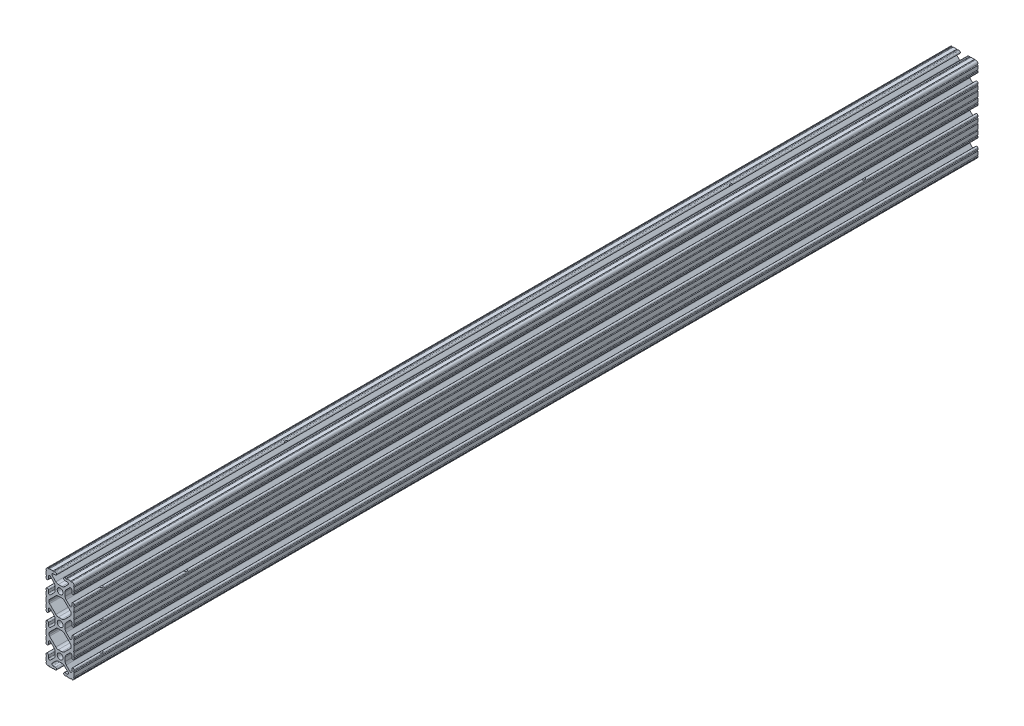
SolidWorks part; units mm, degrees
ref_plane "Front" through (0, 0, 0) normal (0, 0, 1) x (1, 0, 0)
ref_plane "Top" through (0, 0, 0) normal (0, 1, 0) x (1, 0, 0)
ref_plane "Right" through (0, 0, 0) normal (1, 0, 0) x (0, 0, -1)
sketch "Sketch1" plane through (0, 0, 0) normal (0, 0, 1) x (1, 0, 0)
  line L0 (-7.4908, -34.8742) -> (7.4908, -34.8742) construction
  line L1 (-3.1974, -36.9951) -> (3.1974, -36.9951) construction
  line L2 (-7.4908, 34.8742) -> (7.4908, 34.8742) construction
  line L3 (-3.1974, 36.9951) -> (3.1974, 36.9951) construction
  line L16 (-9.9314, -12.1463) -> (-9.9314, -13.2537)
  line L17 (-3.8759, -5.4384) -> (-9.4702, -11.0327)
  line L18 (1.6308, -4.5085) -> (-1.6308, -4.5085)
  line L19 (9.4702, -11.0327) -> (3.8759, -5.4384)
  line L20 (9.9314, -13.2537) -> (9.9314, -12.1463)
  line L21 (3.8759, -19.9616) -> (9.4702, -14.3673)
  line L22 (-1.6308, -20.8915) -> (1.6308, -20.8915)
  line L23 (-9.4702, -14.3673) -> (-3.8759, -19.9616)
  line L32 (-9.9314, 13.2537) -> (-9.9314, 12.1463)
  line L33 (-3.8759, 19.9616) -> (-9.4702, 14.3673)
  line L34 (1.6308, 20.8915) -> (-1.6308, 20.8915)
  line L35 (9.4702, 14.3673) -> (3.8759, 19.9616)
  line L36 (9.9314, 12.1463) -> (9.9314, 13.2537)
  line L37 (3.8759, 5.4384) -> (9.4702, 11.0327)
  line L38 (-1.6308, 4.5085) -> (1.6308, 4.5085)
  line L39 (-9.4702, 11.0327) -> (-3.8759, 5.4384)
  line L152 (-12.7, 34.9504) -> (-12.7, 31.7246)
  line L153 (-12.7, 30.7086) -> (-12.7, 29.7023)
  line L154 (-10.4902, 29.7023) -> (-10.4902, 31.8748)
  line L155 (-8.7558, 32.5932) -> (-5.4384, 29.2759)
  line L156 (-4.5085, 27.0308) -> (-4.5085, 23.7692)
  line L157 (-5.4384, 21.5241) -> (-8.7558, 18.2068)
  line L158 (-10.4902, 18.9252) -> (-10.4902, 21.0977)
  line L159 (-12.7, 21.0977) -> (-12.7, 20.0914)
  line L160 (-12.7, 19.0754) -> (-12.7, 15.8496)
  line L161 (-12.7, 14.8336) -> (-12.7, 10.5664)
  line L162 (-12.7, 9.5504) -> (-12.7, 6.3246)
  line L163 (-12.7, 5.3086) -> (-12.7, 4.3023)
  line L164 (-10.4902, 4.3023) -> (-10.4902, 6.4748)
  line L165 (-8.7558, 7.1932) -> (-5.4384, 3.8759)
  line L166 (-4.5085, 1.6308) -> (-4.5085, -1.6308)
  line L167 (-5.4384, -3.8759) -> (-8.7558, -7.1932)
  line L168 (-10.4902, -6.4748) -> (-10.4902, -4.3023)
  line L169 (-12.7, -4.3023) -> (-12.7, -5.3086)
  line L170 (-12.7, -6.3246) -> (-12.7, -9.5504)
  line L171 (-12.7, -10.5664) -> (-12.7, -14.8336)
  line L172 (-12.7, -15.8496) -> (-12.7, -19.0754)
  line L173 (-12.7, -20.0914) -> (-12.7, -21.0977)
  line L174 (-10.4902, -21.0977) -> (-10.4902, -18.9252)
  line L175 (-8.7558, -18.2068) -> (-5.4384, -21.5241)
  line L176 (-4.5085, -23.7692) -> (-4.5085, -27.0308)
  line L177 (-5.4384, -29.2759) -> (-8.7558, -32.5932)
  line L178 (-10.4902, -31.8748) -> (-10.4902, -29.7023)
  line L179 (-12.7, -29.7023) -> (-12.7, -30.7086)
  line L180 (-12.7, -31.7246) -> (-12.7, -34.9504)
  line L181 (-9.5504, -38.1) -> (-6.3246, -38.1)
  line L182 (-5.3086, -38.1) -> (-4.3023, -38.1)
  line L183 (-4.3023, -35.8902) -> (-6.4748, -35.8902)
  line L184 (-7.1932, -34.1558) -> (-3.8759, -30.8384)
  line L185 (-1.6308, -29.9085) -> (1.6308, -29.9085)
  line L186 (3.8759, -30.8384) -> (7.1932, -34.1558)
  line L187 (6.4748, -35.8902) -> (4.3023, -35.8902)
  line L188 (4.3023, -38.1) -> (5.3086, -38.1)
  line L189 (6.3246, -38.1) -> (9.5504, -38.1)
  line L190 (12.7, -34.9504) -> (12.7, -31.7246)
  line L191 (12.7, -30.7086) -> (12.7, -29.7023)
  line L192 (10.4902, -29.7023) -> (10.4902, -31.8748)
  line L193 (8.7558, -32.5932) -> (5.4384, -29.2759)
  line L194 (4.5085, -27.0308) -> (4.5085, -23.7692)
  line L195 (5.4384, -21.5241) -> (8.7558, -18.2068)
  line L196 (10.4902, -18.9252) -> (10.4902, -21.0977)
  line L197 (12.7, -21.0977) -> (12.7, -20.0914)
  line L198 (12.7, -19.0754) -> (12.7, -15.8496)
  line L199 (12.7, -14.8336) -> (12.7, -10.5664)
  line L200 (12.7, -9.5504) -> (12.7, -6.3246)
  line L201 (12.7, -5.3086) -> (12.7, -4.3023)
  line L202 (10.4902, -4.3023) -> (10.4902, -6.4748)
  line L203 (8.7558, -7.1932) -> (5.4384, -3.8759)
  line L204 (4.5085, -1.6308) -> (4.5085, 1.6308)
  line L205 (5.4384, 3.8759) -> (8.7558, 7.1932)
  line L206 (10.4902, 6.4748) -> (10.4902, 4.3023)
  line L207 (12.7, 4.3023) -> (12.7, 5.3086)
  line L208 (12.7, 6.3246) -> (12.7, 9.5504)
  line L209 (12.7, 10.5664) -> (12.7, 14.8336)
  line L210 (12.7, 15.8496) -> (12.7, 19.0754)
  line L211 (12.7, 20.0914) -> (12.7, 21.0977)
  line L212 (10.4902, 21.0977) -> (10.4902, 18.9252)
  line L213 (8.7558, 18.2068) -> (5.4384, 21.5241)
  line L214 (4.5085, 23.7692) -> (4.5085, 27.0308)
  line L215 (5.4384, 29.2759) -> (8.7558, 32.5932)
  line L216 (10.4902, 31.8748) -> (10.4902, 29.7023)
  line L217 (12.7, 29.7023) -> (12.7, 30.7086)
  line L218 (12.7, 31.7246) -> (12.7, 34.9504)
  line L219 (9.5504, 38.1) -> (6.3246, 38.1)
  line L220 (5.3086, 38.1) -> (4.3023, 38.1)
  line L221 (4.3023, 35.8902) -> (6.4748, 35.8902)
  line L222 (7.1932, 34.1558) -> (3.8759, 30.8384)
  line L223 (1.6308, 29.9085) -> (-1.6308, 29.9085)
  line L224 (-3.8759, 30.8384) -> (-7.1932, 34.1558)
  line L225 (-6.4748, 35.8902) -> (-4.3023, 35.8902)
  line L226 (-4.3023, 38.1) -> (-5.3086, 38.1)
  line L227 (-6.3246, 38.1) -> (-9.5504, 38.1)
  circle A2 centre (0, -25.4) radius 2.6035
  circle A4 centre (0, 0) radius 2.6035
  circle A6 centre (0, 25.4) radius 2.6035
  arc A18 (-9.9314, -13.2537) -> (-9.4702, -14.3673) centre (-8.3566, -13.2537) ccw
  arc A19 (-9.4702, -11.0327) -> (-9.9314, -12.1463) centre (-8.3566, -12.1463) ccw
  arc A20 (-1.6308, -4.5085) -> (-3.8759, -5.4384) centre (-1.6308, -7.6835) ccw
  arc A21 (3.8759, -5.4384) -> (1.6308, -4.5085) centre (1.6308, -7.6835) ccw
  arc A22 (9.9314, -12.1463) -> (9.4702, -11.0327) centre (8.3566, -12.1463) ccw
  arc A23 (9.4702, -14.3673) -> (9.9314, -13.2537) centre (8.3566, -13.2537) ccw
  arc A24 (1.6308, -20.8915) -> (3.8759, -19.9616) centre (1.6308, -17.7165) ccw
  arc A25 (-3.8759, -19.9616) -> (-1.6308, -20.8915) centre (-1.6308, -17.7165) ccw
  arc A36 (-9.9314, 12.1463) -> (-9.4702, 11.0327) centre (-8.3566, 12.1463) ccw
  arc A37 (-9.4702, 14.3673) -> (-9.9314, 13.2537) centre (-8.3566, 13.2537) ccw
  arc A38 (-1.6308, 20.8915) -> (-3.8759, 19.9616) centre (-1.6308, 17.7165) ccw
  arc A39 (3.8759, 19.9616) -> (1.6308, 20.8915) centre (1.6308, 17.7165) ccw
  arc A40 (9.9314, 13.2537) -> (9.4702, 14.3673) centre (8.3566, 13.2537) ccw
  arc A41 (9.4702, 11.0327) -> (9.9314, 12.1463) centre (8.3566, 12.1463) ccw
  arc A42 (1.6308, 4.5085) -> (3.8759, 5.4384) centre (1.6308, 7.6835) ccw
  arc A43 (-3.8759, 5.4384) -> (-1.6308, 4.5085) centre (-1.6308, 7.6835) ccw
  arc A168 (-10.5664, 38.1) -> (-12.7, 35.9664) centre (-10.592, 35.992) ccw
  arc A169 (-12.7, 34.9504) -> (-12.7, 35.9664) centre (-12.7, 35.4584) ccw
  arc A170 (-12.7, 30.7086) -> (-12.7, 31.7246) centre (-12.7, 31.2166) ccw
  arc A171 (-12.7, 29.7023) -> (-10.4902, 29.7023) centre (-11.5951, 29.7023) ccw
  arc A172 (-8.7558, 32.5932) -> (-10.4902, 31.8748) centre (-9.4742, 31.8748) ccw
  arc A173 (-4.5085, 27.0308) -> (-5.4384, 29.2759) centre (-7.6835, 27.0308) ccw
  arc A174 (-5.4384, 21.5241) -> (-4.5085, 23.7692) centre (-7.6835, 23.7692) ccw
  arc A175 (-10.4902, 18.9252) -> (-8.7558, 18.2068) centre (-9.4742, 18.9252) ccw
  arc A176 (-10.4902, 21.0977) -> (-12.7, 21.0977) centre (-11.5951, 21.0977) ccw
  arc A177 (-12.7, 19.0754) -> (-12.7, 20.0914) centre (-12.7, 19.5834) ccw
  arc A178 (-12.7, 14.8336) -> (-12.7, 15.8496) centre (-12.7, 15.3416) ccw
  arc A179 (-12.7, 9.5504) -> (-12.7, 10.5664) centre (-12.7, 10.0584) ccw
  arc A180 (-12.7, 5.3086) -> (-12.7, 6.3246) centre (-12.7, 5.8166) ccw
  arc A181 (-12.7, 4.3023) -> (-10.4902, 4.3023) centre (-11.5951, 4.3023) ccw
  arc A182 (-8.7558, 7.1932) -> (-10.4902, 6.4748) centre (-9.4742, 6.4748) ccw
  arc A183 (-4.5085, 1.6308) -> (-5.4384, 3.8759) centre (-7.6835, 1.6308) ccw
  arc A184 (-5.4384, -3.8759) -> (-4.5085, -1.6308) centre (-7.6835, -1.6308) ccw
  arc A185 (-10.4902, -6.4748) -> (-8.7558, -7.1932) centre (-9.4742, -6.4748) ccw
  arc A186 (-10.4902, -4.3023) -> (-12.7, -4.3023) centre (-11.5951, -4.3023) ccw
  arc A187 (-12.7, -6.3246) -> (-12.7, -5.3086) centre (-12.7, -5.8166) ccw
  arc A188 (-12.7, -10.5664) -> (-12.7, -9.5504) centre (-12.7, -10.0584) ccw
  arc A189 (-12.7, -15.8496) -> (-12.7, -14.8336) centre (-12.7, -15.3416) ccw
  arc A190 (-12.7, -20.0914) -> (-12.7, -19.0754) centre (-12.7, -19.5834) ccw
  arc A191 (-12.7, -21.0977) -> (-10.4902, -21.0977) centre (-11.5951, -21.0977) ccw
  arc A192 (-8.7558, -18.2068) -> (-10.4902, -18.9252) centre (-9.4742, -18.9252) ccw
  arc A193 (-4.5085, -23.7692) -> (-5.4384, -21.5241) centre (-7.6835, -23.7692) ccw
  arc A194 (-5.4384, -29.2759) -> (-4.5085, -27.0308) centre (-7.6835, -27.0308) ccw
  arc A195 (-10.4902, -31.8748) -> (-8.7558, -32.5932) centre (-9.4742, -31.8748) ccw
  arc A196 (-10.4902, -29.7023) -> (-12.7, -29.7023) centre (-11.5951, -29.7023) ccw
  arc A197 (-12.7, -31.7246) -> (-12.7, -30.7086) centre (-12.7, -31.2166) ccw
  arc A198 (-12.7, -35.9664) -> (-12.7, -34.9504) centre (-12.7, -35.4584) ccw
  arc A199 (-12.7, -35.9664) -> (-10.5664, -38.1) centre (-10.592, -35.992) ccw
  arc A200 (-9.5504, -38.1) -> (-10.5664, -38.1) centre (-10.0584, -38.1) ccw
  arc A201 (-5.3086, -38.1) -> (-6.3246, -38.1) centre (-5.8166, -38.1) ccw
  arc A202 (-4.3023, -38.1) -> (-4.3023, -35.8902) centre (-4.3023, -36.9951) ccw
  arc A203 (-7.1932, -34.1558) -> (-6.4748, -35.8902) centre (-6.4748, -34.8742) ccw
  arc A204 (-1.6308, -29.9085) -> (-3.8759, -30.8384) centre (-1.6308, -33.0835) ccw
  arc A205 (3.8759, -30.8384) -> (1.6308, -29.9085) centre (1.6308, -33.0835) ccw
  arc A206 (6.4748, -35.8902) -> (7.1932, -34.1558) centre (6.4748, -34.8742) ccw
  arc A207 (4.3023, -35.8902) -> (4.3023, -38.1) centre (4.3023, -36.9951) ccw
  arc A208 (6.3246, -38.1) -> (5.3086, -38.1) centre (5.8166, -38.1) ccw
  arc A209 (10.5664, -38.1) -> (9.5504, -38.1) centre (10.0584, -38.1) ccw
  arc A210 (10.5664, -38.1) -> (12.7, -35.9664) centre (10.592, -35.992) ccw
  arc A211 (12.7, -34.9504) -> (12.7, -35.9664) centre (12.7, -35.4584) ccw
  arc A212 (12.7, -30.7086) -> (12.7, -31.7246) centre (12.7, -31.2166) ccw
  arc A213 (12.7, -29.7023) -> (10.4902, -29.7023) centre (11.5951, -29.7023) ccw
  arc A214 (8.7558, -32.5932) -> (10.4902, -31.8748) centre (9.4742, -31.8748) ccw
  arc A215 (4.5085, -27.0308) -> (5.4384, -29.2759) centre (7.6835, -27.0308) ccw
  arc A216 (5.4384, -21.5241) -> (4.5085, -23.7692) centre (7.6835, -23.7692) ccw
  arc A217 (10.4902, -18.9252) -> (8.7558, -18.2068) centre (9.4742, -18.9252) ccw
  arc A218 (10.4902, -21.0977) -> (12.7, -21.0977) centre (11.5951, -21.0977) ccw
  arc A219 (12.7, -19.0754) -> (12.7, -20.0914) centre (12.7, -19.5834) ccw
  arc A220 (12.7, -14.8336) -> (12.7, -15.8496) centre (12.7, -15.3416) ccw
  arc A221 (12.7, -9.5504) -> (12.7, -10.5664) centre (12.7, -10.0584) ccw
  arc A222 (12.7, -5.3086) -> (12.7, -6.3246) centre (12.7, -5.8166) ccw
  arc A223 (12.7, -4.3023) -> (10.4902, -4.3023) centre (11.5951, -4.3023) ccw
  arc A224 (8.7558, -7.1932) -> (10.4902, -6.4748) centre (9.4742, -6.4748) ccw
  arc A225 (4.5085, -1.6308) -> (5.4384, -3.8759) centre (7.6835, -1.6308) ccw
  arc A226 (5.4384, 3.8759) -> (4.5085, 1.6308) centre (7.6835, 1.6308) ccw
  arc A227 (10.4902, 6.4748) -> (8.7558, 7.1932) centre (9.4742, 6.4748) ccw
  arc A228 (10.4902, 4.3023) -> (12.7, 4.3023) centre (11.5951, 4.3023) ccw
  arc A229 (12.7, 6.3246) -> (12.7, 5.3086) centre (12.7, 5.8166) ccw
  arc A230 (12.7, 10.5664) -> (12.7, 9.5504) centre (12.7, 10.0584) ccw
  arc A231 (12.7, 15.8496) -> (12.7, 14.8336) centre (12.7, 15.3416) ccw
  arc A232 (12.7, 20.0914) -> (12.7, 19.0754) centre (12.7, 19.5834) ccw
  arc A233 (12.7, 21.0977) -> (10.4902, 21.0977) centre (11.5951, 21.0977) ccw
  arc A234 (8.7558, 18.2068) -> (10.4902, 18.9252) centre (9.4742, 18.9252) ccw
  arc A235 (4.5085, 23.7692) -> (5.4384, 21.5241) centre (7.6835, 23.7692) ccw
  arc A236 (5.4384, 29.2759) -> (4.5085, 27.0308) centre (7.6835, 27.0308) ccw
  arc A237 (10.4902, 31.8748) -> (8.7558, 32.5932) centre (9.4742, 31.8748) ccw
  arc A238 (10.4902, 29.7023) -> (12.7, 29.7023) centre (11.5951, 29.7023) ccw
  arc A239 (12.7, 31.7246) -> (12.7, 30.7086) centre (12.7, 31.2166) ccw
  arc A240 (12.7, 35.9664) -> (12.7, 34.9504) centre (12.7, 35.4584) ccw
  arc A241 (12.7, 35.9664) -> (10.5664, 38.1) centre (10.592, 35.992) ccw
  arc A242 (9.5504, 38.1) -> (10.5664, 38.1) centre (10.0584, 38.1) ccw
  arc A243 (5.3086, 38.1) -> (6.3246, 38.1) centre (5.8166, 38.1) ccw
  arc A244 (4.3023, 38.1) -> (4.3023, 35.8902) centre (4.3023, 36.9951) ccw
  arc A245 (7.1932, 34.1558) -> (6.4748, 35.8902) centre (6.4748, 34.8742) ccw
  arc A246 (1.6308, 29.9085) -> (3.8759, 30.8384) centre (1.6308, 33.0835) ccw
  arc A247 (-3.8759, 30.8384) -> (-1.6308, 29.9085) centre (-1.6308, 33.0835) ccw
  arc A248 (-6.4748, 35.8902) -> (-7.1932, 34.1558) centre (-6.4748, 34.8742) ccw
  arc A249 (-4.3023, 35.8902) -> (-4.3023, 38.1) centre (-4.3023, 36.9951) ccw
  arc A250 (-6.3246, 38.1) -> (-5.3086, 38.1) centre (-5.8166, 38.1) ccw
  arc A251 (-10.5664, 38.1) -> (-9.5504, 38.1) centre (-10.0584, 38.1) ccw
extrude "Boss-Extrude1" add sketch "Sketch1" along normal mid plane 812.8
sketch "Sketch2" plane through (4.5085, 0, 0) normal (1, 0, 0) x (0, 0, -1)
  line L0 (-406.4, 38.1) -> (406.4, 38.1) construction
  line L1 (-406.4, 23.7692) -> (-406.4, 27.0308) construction
  line L2 (-406.4, -1.6308) -> (-406.4, 1.6308) construction
  line L3 (-406.4, -27.0308) -> (-406.4, -23.7692) construction
  circle A0 centre (-381, 25.4) radius 3.5
  circle A1 centre (-381, 0) radius 3.5
  circle A2 centre (-381, -25.4) radius 3.5
  dimension "D1" = 7
  dimension "D2" = 12.7
  dimension "D3" = 25.4
  dimension "D4" = 7
  dimension "D5" = 7
  dimension "D6" = 25.4
  dimension "D7" = 25.4
  dimension "D8" = 25.4
  dimension "D9" = 25.4
extrude "Cut-Extrude1" cut sketch "Sketch2" against normal through all both and the other way through all
sketch "Sketch3" plane through (4.5085, 0, 0) normal (1, 0, 0) x (0, 0, -1)
  line L0 (0, 0) -> (0, 69.8838) construction
  line L1 (-406.4, -1.6308) -> (-406.4, 1.6308) construction
  line L2 (-406.4, 38.1) -> (406.4, 38.1) construction
  circle A0 centre (-304.8, 0) radius 3.5
  circle A1 centre (304.8, 0) radius 3.5
  dimension "D1" = 7
  dimension "D2" = 101.6
  dimension "D3" = 38.1
extrude "Cut-Extrude2" cut sketch "Sketch3" against normal through all both and the other way through all
sketch "Sketch4" plane through (0, -29.9085, 0) normal (0, -1, 0) x (1, 0, 0)
  line L0 (0, 0) -> (131.3157, 0) construction
  circle A0 centre (0, 200) radius 3.5
  circle A1 centre (0, -200) radius 3.5
  point P5 (131.3157, 0)
  dimension "D1" = 7
  dimension "D2" = 200
extrude "Cut-Extrude3" cut sketch "Sketch4" against normal through all both and the other way through all
